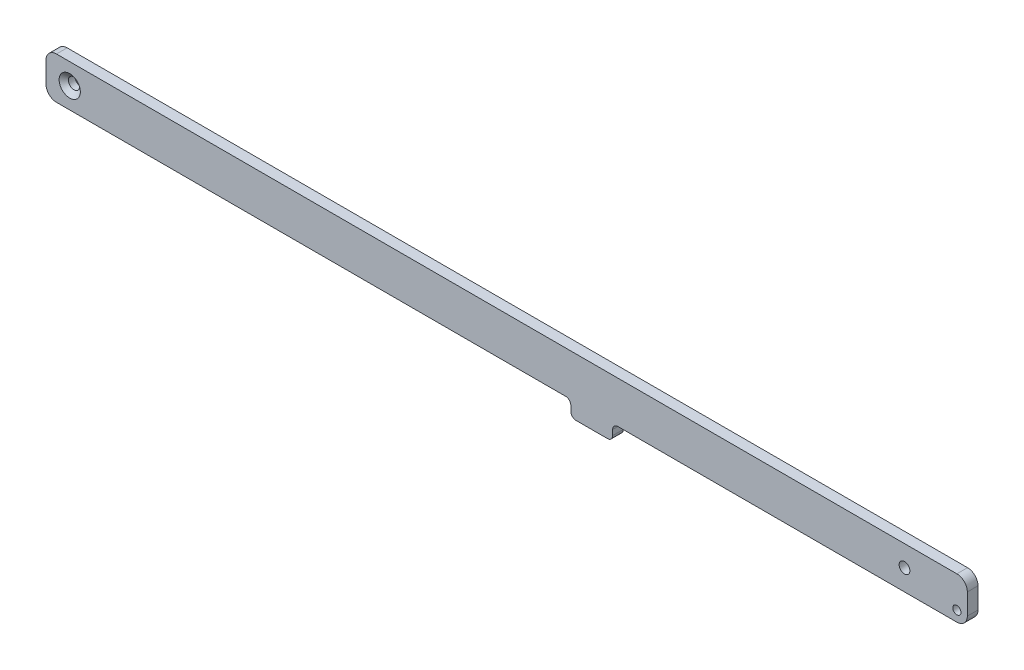
SolidWorks part; units mm, degrees
material "PC High Viscosity"
ref_plane "Front Plane" through (0, 0, 0) normal (0, 0, 1) x (1, 0, 0)
ref_plane "Top Plane" through (0, 0, 0) normal (0, 1, 0) x (1, 0, 0)
ref_plane "Right Plane" through (0, 0, 0) normal (1, 0, 0) x (0, 0, -1)
sketch "Sketch1" plane through (0, 0, 0) normal (0, 0, 1) x (1, 0, 0)
  line L1 (0, 0) -> (40.5308, 0)
  line L2 (0, 0) -> (0, 25.4)
  line L3 (0, 25.4) -> (40.5307, 25.4)
  line L4 (558.8, 0) -> (558.8, 25.4)
  line L11 (558.8, 10.0162) -> (552.45, 13.6823) construction
  line L12 (552.45, 13.6823) -> (546.1, 10.0162) construction
  line L13 (546.1, 10.0162) -> (546.1, 2.6838) construction
  line L14 (546.1, 2.6838) -> (552.45, -0.9823) construction
  line L15 (552.45, -0.9823) -> (558.8, 2.6838) construction
  line L16 (558.8, 2.6838) -> (558.8, 10.0162) construction
  line L19 (40.5307, 25.4) -> (558.8, 25.4)
  line L20 (40.5308, 0) -> (318.3103, 0)
  line L21 (343.7103, 0) -> (343.7103, -9.525)
  line L22 (343.7103, -9.525) -> (318.3103, -9.525)
  line L23 (318.3103, -9.525) -> (318.3103, 0)
  line L24 (343.7103, 0) -> (558.8, 0)
  circle A0 centre (552.45, 6.35) radius 2.4892
  circle A1 centre (552.45, 6.35) radius 6.35 construction
  dimension "D5" = 4.9784
  dimension "D7" = 12.7
  dimension "D1" = 558.8
  dimension "D2" = 25.4
  dimension "D3" = 25.4
  dimension "D4" = 9.525
  dimension "D8" = 318.3103
extrude "Boss-Extrude1" add sketch "Sketch1" along normal blind 6.477 contours L3 | L1 L4 L3 L2 A0 | L1 region at (279.8974, 12.4155, 0)
fillet "Fillet2" radius 6.35 4 edges at (558.8, 25.4, 3.2385) (0, 0, 3.2385) (0, 25.4, 3.2385) (558.8, 0, 3.2385)
sketch "Sketch2" plane through (0, 0, 6.477) normal (0, 0, 1) x (1, 0, 0)
  line L2 (558.8, 6.35) -> (558.8, 19.05) construction
  line L3 (6.35, 25.4) -> (552.45, 25.4) construction
  circle A0 centre (520.7, 12.7) radius 3.2639
  point P4 (0, 0)
  dimension "D1" = 6.5278
  dimension "D2" = 38.1
  dimension "D3" = 12.7
fillet "Fillet3" radius 3.175 4 edges at (318.3103, 0, 3.2385) (318.3103, -9.525, 3.2385) (343.7103, -9.525, 3.2385) (343.7103, 0, 3.2385)
hole_wizard "CSK for 1/4 Flat Head Machine Screw (100)2" positions "Sketch6" profile "Sketch7" countersink size "1/4" standard "ANSI Inch"
sketch "Sketch6" plane through (0, 0, 6.477) normal (0, 0, 1) x (1, 0, 0)
  line L2 (0, 6.35) -> (0, 19.05) construction
  line L3 (6.35, 0) -> (315.1353, 0) construction
  point P0 (14.3939, 12.7)
  point P11 (14.3939, 12.7)
  dimension "D1" = 14.3939
  dimension "D2" = 12.7
sketch "Sketch7" plane through (14.3939, 12.7, 6.477) normal (1, 0, 0) x (0, -1, 0)
  line L0 (0, 0) -> (0, 21.0798)
  line L1 (0, 21.0798) -> (3.3782, 19.05)
  line L2 (3.3782, 19.05) -> (3.3782, 2.5682)
  line L3 (3.3782, 2.5682) -> (6.4389, 0)
  line L5 (6.4389, 0) -> (0, 0)
  line L6 (-3.3782, 2.5682) -> (-6.4389, 0) construction
  line L10 (0, 21.0798) -> (-3.3782, 19.05) construction
  line L11 (0, -6.35) -> (0, 107.95) construction
  dimension "Hole Dia." = 6.7564
  dimension "Hole Depth" = 19.05
  dimension "Near C'Sink Dia." = 12.8778
  dimension "Near C'Sink Angle" = 100
  dimension "Drill Angle" = 118
extrude "Cut-Extrude1" cut sketch "Sketch2" against normal through all
